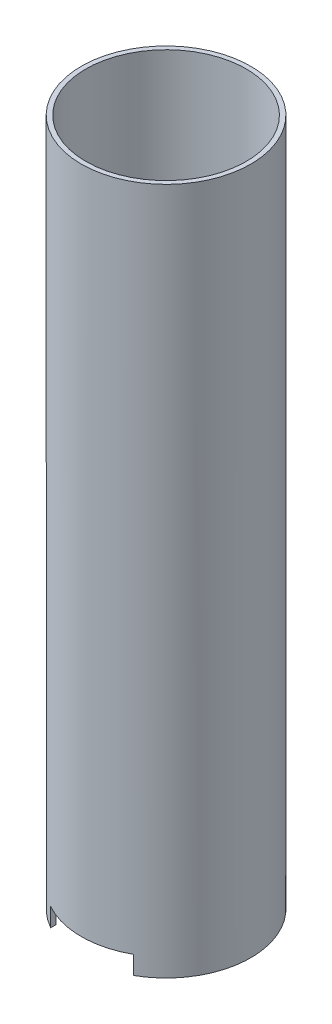
SolidWorks part; units mm, degrees
ref_plane "Front Plane" through (0, 0, 0) normal (0, 0, 1) x (1, 0, 0)
ref_plane "Top Plane" through (0, 0, 0) normal (0, 1, 0) x (1, 0, 0)
ref_plane "Right Plane" through (0, 0, 0) normal (1, 0, 0) x (0, 0, -1)
sketch "Sketch1" plane through (0, 0, 0) normal (0, 1, 0) x (1, 0, 0)
  line L0 (-17.5, 0) -> (17.5, 0) construction
  line L1 (0, 17.5) -> (0, 15) construction
  line L2 (-9.0139, 15) -> (9.0139, 15)
  line L3 (-9.0139, -15) -> (9.0139, -15)
  line L4 (-9.0139, 15) -> (-9.0139, 16.1555)
  line L5 (9.0139, 15) -> (9.0139, 16.1555)
  line L6 (-9.0139, -15) -> (-9.0139, -16.1555)
  line L7 (9.0139, -15) -> (9.0139, -16.1555)
  circle A0 centre (0, 0) radius 18.5
  circle A1 centre (0, 0) radius 17.5
  circle A2 centre (0, 0) radius 6.5 construction
  dimension "D1" = 37
  dimension "D2" = 35
  dimension "D4" = 13
  dimension "D3" = 2.5
extrude "Shell" add sketch "Sketch1" along normal blind 150 contours A1 L4 A0 L6 | A1 L6 A0 L7 | A1 L5 A0 L4 | A1 L7 A0 L5 region at (-17.8367, 0, 0) region at (-8.8302, 0, -15.5777) region at (9.3506, 0, -15.5777) region at (0, 0, 17.6836)
ref_plane "Plane3" through (0, 120, 0) normal (0, 1, 0) x (1, 0, 0)
sketch "Sketch8" plane through (0, 120, 0) normal (0, 1, 0) x (1, 0, 0)
  line L0 (0, -12) -> (0, 0) construction
  circle A0 centre (0, 0) radius 17.5
  circle A2 centre (0, -12) radius 3.5
  circle A3 centre (0, 0) radius 6.5
  dimension "D1" = 12
  dimension "D2" = 7
  dimension "D3" = 35
  dimension "D4" = 13
extrude "RodAligner" add sketch "Sketch8" along normal mid plane 2
extrude "Cut-Extrude1" cut sketch "Sketch1<7>" along normal blind 4 contours A1 L5 A0 L4 | A1 L6 A0 L7 region at (-8.8302, 0, -15.5777) region at (0, 0, 17.6836)
sketch "Sketch1<7>" plane through (0, 0, 0) normal (0, 1, 0) x (1, 0, 0) same geometry as "Sketch1"
